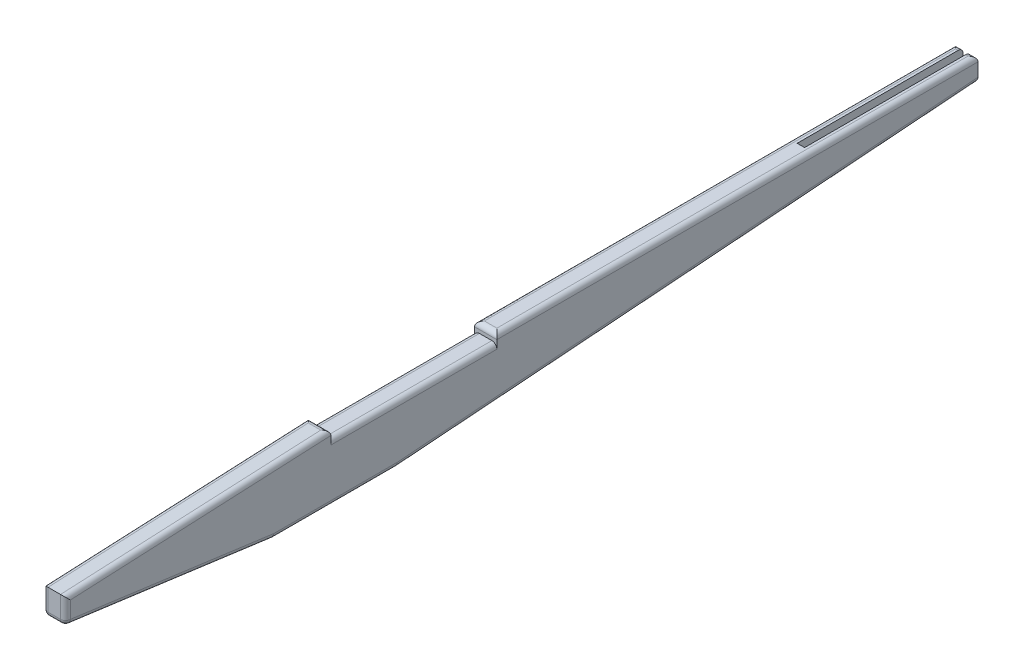
SolidWorks part; units mm, degrees
material "Balsa"
ref_plane "Front" through (0, 0, 0) normal (0, 0, 1) x (1, 0, 0)
ref_plane "Top" through (0, 0, 0) normal (0, 1, 0) x (1, 0, 0)
ref_plane "Right" through (0, 0, 0) normal (1, 0, 0) x (0, 0, -1)
sketch "Sketch1" plane through (0, 0, 0) normal (1, 0, 0) x (0, 0, -1)
  line L0 (0, 16.9) -> (0, 32.5)
  line L1 (0, 32.5) -> (160, 40)
  line L2 (160, 40) -> (550, 40)
  line L3 (550, 40) -> (550, 26)
  line L4 (550, 26) -> (200, 0)
  line L5 (200, 0) -> (125.3, 0)
  line L6 (125.3, 0) -> (0, 16.9)
  dimension "D1" = 15.6
  dimension "D2" = 40
  dimension "D3" = 7.5
  dimension "D4" = 550
  dimension "D5" = 160
  dimension "D6" = 125.3
  dimension "D7" = 200
  dimension "D8" = 14
extrude "Boss-Extrude1" add sketch "Sketch1" along normal blind 13.5
sketch "Sketch2" plane through (13.5, 0, 0) normal (1, 0, 0) x (0, 0, -1)
  line L0 (125.3, 0) -> (200, 0) construction
  line L1 (160, 40) -> (260, 40)
  line L2 (160, 40) -> (160, 35)
  line L3 (160, 35) -> (260, 35)
  line L4 (260, 40) -> (260, 35)
  dimension "D1" = 35
  dimension "D2" = 100
extrude "Cut-Extrude1" cut sketch "Sketch2" against normal through all
sketch "Sketch3" plane through (0, 40, 0) normal (0, 1, 0) x (1, 0, 0)
  line L0 (13.5, 550) -> (0, 550) construction
  line L1 (4.5, 550) -> (9, 550)
  line L2 (4.5, 550) -> (4.5, 450)
  line L3 (4.5, 450) -> (9, 450)
  line L4 (9, 550) -> (9, 450)
  line L5 (0, 550) -> (0, 260) construction
  line L6 (13.5, 550) -> (13.5, 260) construction
  dimension "D1" = 100
  dimension "D2" = 4.5
  dimension "D3" = 4.5
extrude "Cut-Extrude2" cut sketch "Sketch3" against normal blind 5
fillet "Fillet1" radius 3 21 edges at (11.25, 40, -550) (2.25, 40, -550) (6.75, 26, -550) (0, 13, -375) (0, 0, -162.65) (13.5, 13, -375) (13.5, 0, -162.65) (6.75, 0, -125.3) (0, 8.45, -62.65) (6.75, 16.9, 0) (0, 24.7, 0) (13.5, 24.7, 0) (13.5, 8.45, -62.65) (0, 35, -210) (13.5, 35, -210) (0, 40, -405) (13.5, 40, -405) (6.75, 40, -260) (6.75, 40, -160) (0, 36.25, -80) (13.5, 36.25, -80)
